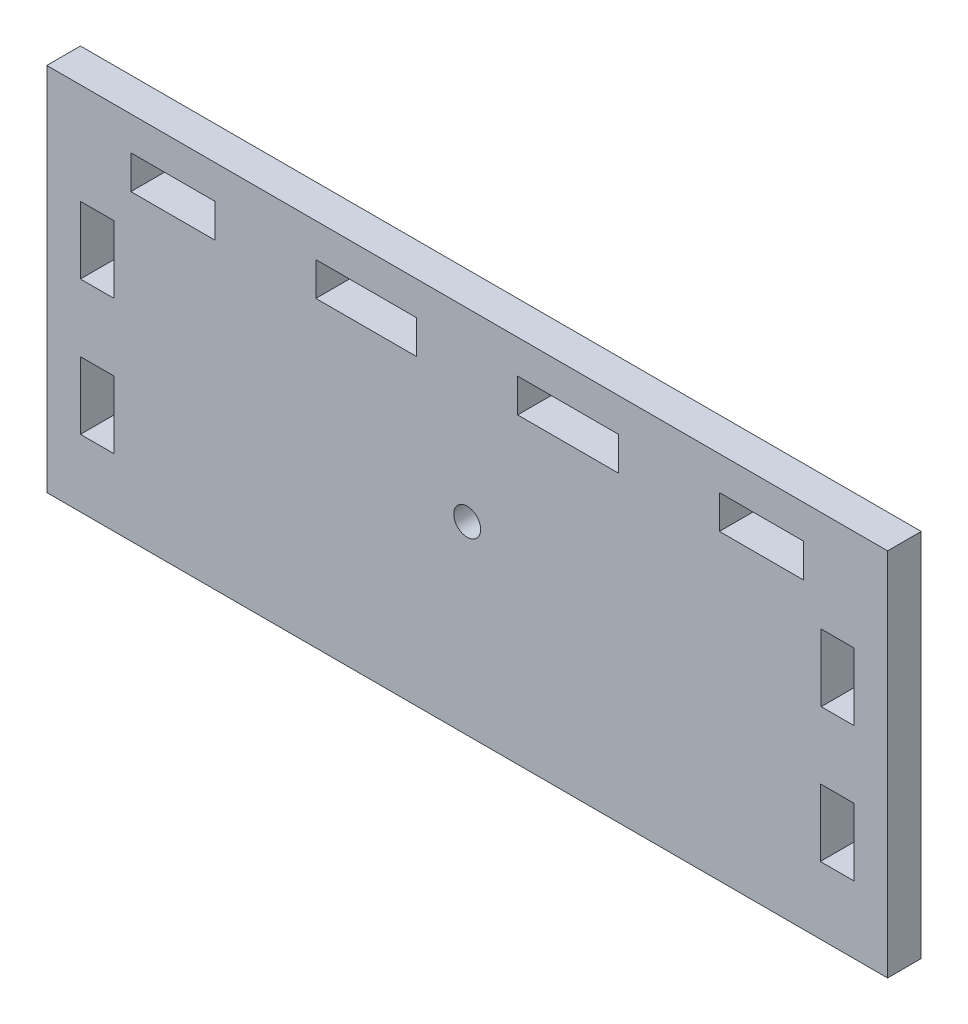
SolidWorks part; units mm, degrees
ref_plane "Plan de face" through (0, 0, 0) normal (0, 0, 1) x (1, 0, 0)
ref_plane "Plan de dessus" through (0, 0, 0) normal (0, 1, 0) x (1, 0, 0)
ref_plane "Plan de droite" through (0, 0, 0) normal (1, 0, 0) x (0, 0, -1)
sketch "Esquisse1" plane through (0, 0, 0) normal (0, 0, 1) x (1, 0, 0)
  line L0 (-66.6112, 37.3798) -> (58.3888, -17.6202) construction
  line L1 (58.3888, -17.6202) -> (-66.6112, -17.6202)
  line L2 (58.3888, -17.6202) -> (58.3888, 37.3798)
  line L3 (58.3888, 37.3798) -> (-66.6112, 37.3798)
  line L4 (-66.6112, -17.6202) -> (-66.6112, 37.3798)
  line L5 (58.3888, 37.3798) -> (-66.6112, -17.6202) construction
  dimension "D1" = 125
  dimension "D2" = 55
extrude "Boss.-Extru.3" add sketch "Esquisse1" along normal blind 5
sketch "Esquisse2" plane through (0, 0, 5) normal (0, 0, 1) x (1, 0, 0)
  line L0 (-66.6112, 37.3798) -> (58.3888, -17.6202) construction
  line L1 (58.3888, -17.6202) -> (58.3888, 37.3798) construction
  line L2 (58.3888, 37.3798) -> (-66.6112, -17.6202) construction
  circle A0 centre (-4.1112, 9.8798) radius 2
  dimension "D1" = 4
extrude "Enlèv. mat.-Extru.1" cut sketch "Esquisse2" against normal blind 3
sketch "Esquisse3" plane through (0, 0, 5) normal (0, 0, 1) x (1, 0, 0)
  line L0 (58.3888, -17.6202) -> (58.3888, 37.3798) construction
  line L1 (53.3888, 22.3798) -> (48.5204, 22.3798)
  line L2 (53.3888, 22.3798) -> (53.3888, 12.3798)
  line L3 (53.3888, 12.3798) -> (48.5204, 12.3798)
  line L4 (48.5204, 22.3798) -> (48.5204, 12.3798)
  line L5 (58.3888, 37.3798) -> (-66.6112, 37.3798) construction
  line L6 (-66.6112, 37.3798) -> (-66.6112, -17.6202) construction
  line L7 (53.3888, 2.3798) -> (48.3888, 2.3798)
  line L8 (53.3888, 2.3798) -> (53.3888, -7.6202)
  line L9 (53.3888, -7.6202) -> (48.3888, -7.6202)
  line L10 (48.3888, 2.3798) -> (48.3888, -7.6202)
  line L11 (-56.6112, 22.3798) -> (-61.6112, 22.3798)
  line L12 (-56.6112, 22.3798) -> (-56.6112, 12.3798)
  line L13 (-56.6112, 12.3798) -> (-61.6112, 12.3798)
  line L14 (-61.6112, 22.3798) -> (-61.6112, 12.3798)
  line L15 (-66.6112, 37.3798) -> (-66.6112, -17.6202) construction
  line L16 (-56.6112, 2.3798) -> (-61.6112, 2.3798)
  line L17 (-56.6112, 2.3798) -> (-56.6112, -7.6202)
  line L18 (-56.6112, -7.6202) -> (-61.6112, -7.6202)
  line L19 (-61.6112, 2.3798) -> (-61.6112, -7.6202)
  line L20 (-54.1112, 32.3798) -> (-41.6112, 32.3798)
  line L21 (-54.1112, 32.3798) -> (-54.1112, 27.3798)
  line L22 (-54.1112, 27.3798) -> (-41.6112, 27.3798)
  line L23 (-41.6112, 32.3798) -> (-41.6112, 27.3798)
  line L25 (-26.6112, 32.3798) -> (-11.6112, 32.3798)
  line L26 (-26.6112, 32.3798) -> (-26.6112, 27.3798)
  line L27 (-26.6112, 27.3798) -> (-11.6112, 27.3798)
  line L28 (-11.6112, 32.3798) -> (-11.6112, 27.3798)
  line L29 (3.3888, 32.3798) -> (18.3888, 32.3798)
  line L30 (3.3888, 32.3798) -> (3.3888, 27.3798)
  line L31 (3.3888, 27.3798) -> (18.3888, 27.3798)
  line L32 (18.3888, 32.3798) -> (18.3888, 27.3798)
  line L33 (33.3888, 32.3798) -> (45.8888, 32.3798)
  line L34 (33.3888, 32.3798) -> (33.3888, 27.3798)
  line L35 (33.3888, 27.3798) -> (45.8888, 27.3798)
  line L36 (45.8888, 32.3798) -> (45.8888, 27.3798)
  dimension "D1" = 10
  dimension "D2" = 4.8684
  dimension "D3" = 5
  dimension "D4" = 15
  dimension "D5" = 10
  dimension "D6" = 5
  dimension "D7" = 5
  dimension "D8" = 10
  dimension "D9" = 15
  dimension "D10" = 10
  dimension "D11" = 5
  dimension "D12" = 5
  dimension "D13" = 5
  dimension "D14" = 10
  dimension "D15" = 5
  dimension "D16" = 12.5
  dimension "D17" = 5
  dimension "D18" = 12.5
  dimension "D19" = 5
  dimension "D20" = 15
  dimension "D21" = 15
  dimension "D22" = 5
  dimension "D23" = 5
  dimension "D24" = 15
  dimension "D25" = 15
  dimension "D26" = 12.5
  dimension "D27" = 15
  dimension "D28" = 10
extrude "Enlèv. mat.-Extru.2" cut sketch "Esquisse3" against normal blind 5 contours L12 L13 L14 L11 | L10 L9 L8 L7 | L4 L3 L2 L1 | L17 L18 L19 L16 | L27 L28 L25 L26 | L22 L23 L20 L21 | L35 L36 L33 L34 | L31 L32 L29 L30
